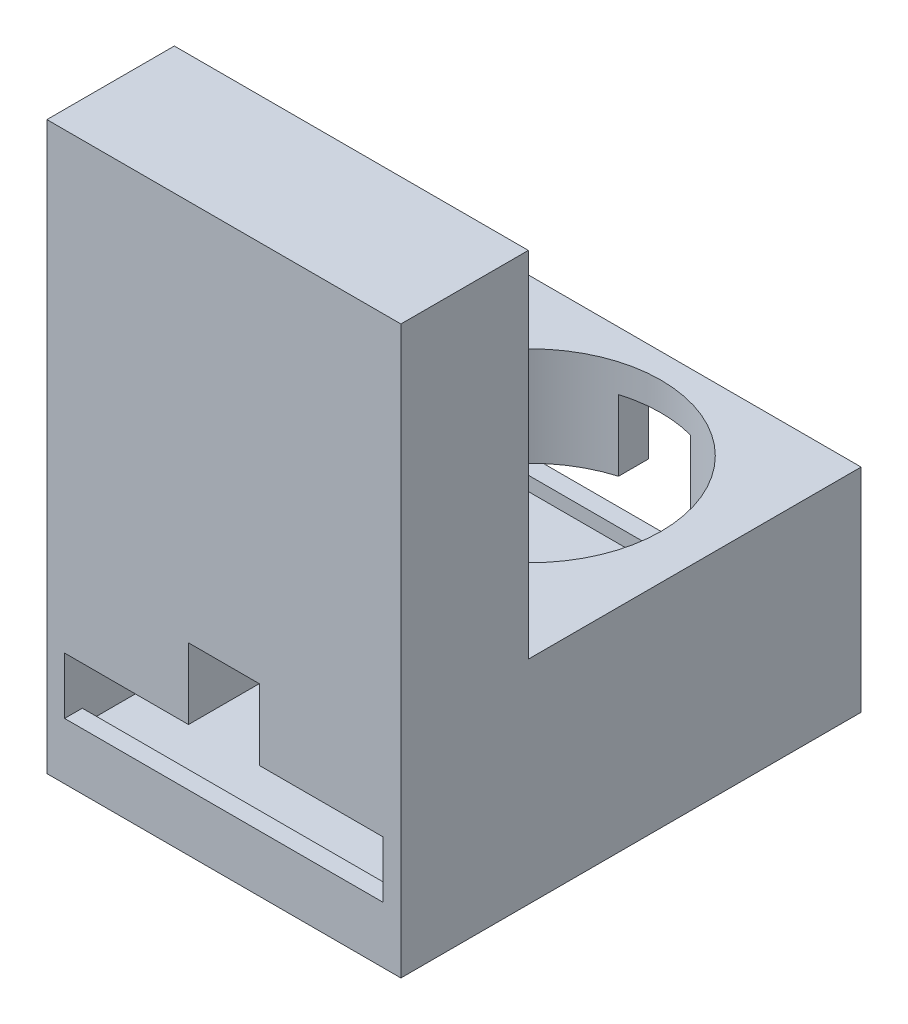
SolidWorks part; units mm, degrees
ref_plane "Front Plane" through (0, 0, 0) normal (0, 0, 1) x (1, 0, 0)
ref_plane "Top Plane" through (0, 0, 0) normal (0, 1, 0) x (1, 0, 0)
ref_plane "Right Plane" through (0, 0, 0) normal (1, 0, 0) x (0, 0, -1)
sketch "Sketch1" plane through (0, 0, 0) normal (0, 1, 0) x (1, 0, 0)
  line L1 (0, 0) -> (50, 0)
  line L2 (0, 0) -> (0, 65)
  line L3 (0, 65) -> (50, 65)
  line L4 (50, 0) -> (50, 65)
  dimension "D1" = 50
  dimension "D2" = 65
extrude "Boss-Extrude1" add sketch "Sketch1" along normal blind 30
sketch "Sketch3" plane through (0, 0, 0) normal (0, 0, 1) x (1, 0, 0)
  line L0 (0, 0) -> (50, 0) construction
  line L1 (2.5, 8) -> (47.5, 8)
  line L2 (2.5, 8) -> (2.5, 16)
  line L3 (2.5, 16) -> (47.5, 16)
  line L4 (47.5, 8) -> (47.5, 16)
  line L5 (25, 16) -> (25, 26) construction
  line L6 (20, 16) -> (30, 16)
  line L7 (20, 16) -> (20, 26)
  line L8 (20, 26) -> (30, 26)
  line L9 (30, 16) -> (30, 26)
  line L11 (25, 0) -> (25, 8) construction
  point P12 (25, 26)
  dimension "D1" = 8
  dimension "D2" = 8
  dimension "D3" = 10
  dimension "D4" = 10
  dimension "D5" = 45
extrude "Cut-Extrude4" cut sketch "Sketch3" against normal through all contours L3 L9 L8 L7 | L1 L4 L3 L2 region at (25, 12, 0) region at (25, 21, 0)
sketch "Sketch4" plane through (47.5, 0, 0) normal (-1, 0, 0) x (0, 0, 1)
  line L0 (-65, 8) -> (0, 8) construction
  line L1 (-62.5, 8) -> (-2.5, 8)
  line L2 (-62.5, 8) -> (-62.5, 6)
  line L3 (-62.5, 6) -> (-2.5, 6)
  line L4 (-2.5, 8) -> (-2.5, 6)
  point P6 (-32.5, 8)
  point P7 (-32.5, 8)
  dimension "D1" = 60
  dimension "D2" = 2
extrude "Cut-Extrude5" cut sketch "Sketch4" along normal up to surface (45 mm away) up to face at (2.5, 12, -32.5)
sketch "Sketch5" plane through (0, 30, 0) normal (0, 1, 0) x (1, 0, 0)
  line L0 (50, 65) -> (0, 65) construction
  circle A0 centre (25.2445, 43) radius 18.5
  dimension "D1" = 37
  dimension "D2" = 22
extrude "Cut-Extrude6" cut sketch "Sketch5" against normal up to surface (14 mm away) up to face at (11.25, 16, -32.5)
sketch "Sketch6" plane through (0, 30, 0) normal (0, 1, 0) x (1, 0, 0)
  line L0 (50, 0) -> (50, 65) construction
  line L1 (0, 0) -> (50, 0)
  line L2 (0, 0) -> (0, 18)
  line L3 (0, 18) -> (50, 18)
  line L4 (50, 0) -> (50, 18)
  circle A0 centre (25.2445, 43) radius 18.5 construction
  dimension "D1" = 25
extrude "Boss-Extrude2" add sketch "Sketch6" along normal blind 50
